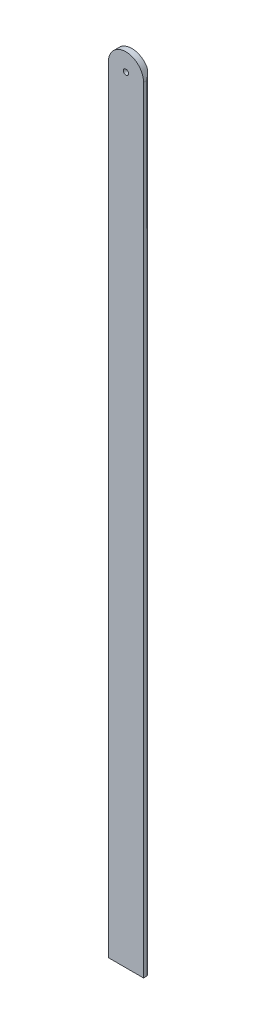
SolidWorks part; units mm, degrees
material "6061 Alloy"
ref_plane "Front Plane" through (0, 0, 0) normal (0, 0, 1) x (1, 0, 0)
ref_plane "Top Plane" through (0, 0, 0) normal (0, 1, 0) x (1, 0, 0)
ref_plane "Right Plane" through (0, 0, 0) normal (1, 0, 0) x (0, 0, -1)
sketch "Sketch2" plane through (0, 0, 0) normal (0, 1, 0) x (1, 0, 0)
  line L0 (0, 0) -> (19.05, 0)
  line L1 (0, 0) -> (0, 19.05)
  line L2 (4.7625, 3.175) -> (17.4625, 3.175)
  line L3 (3.175, 4.7625) -> (3.175, 17.4625)
  line L4 (0, 19.05) -> (1.5875, 19.05)
  line L5 (19.05, 1.5875) -> (19.05, 0)
  line L6 (3.175, 3.175) -> (3.175, 19.05) construction
  line L7 (3.175, 3.175) -> (19.05, 3.175) construction
  arc A0 (3.175, 17.4625) -> (1.5875, 19.05) centre (1.5875, 17.4625) ccw
  arc A1 (3.175, 4.7625) -> (4.7625, 3.175) centre (4.7625, 4.7625) ccw
  arc A2 (17.4625, 3.175) -> (19.05, 1.5875) centre (17.4625, 1.5875) cw
  dimension "D2" = 1.5875
  dimension "D1" = 3.175
extrude "Boss-Extrude1" add sketch "Sketch2" along normal blind 431.8
sketch "Sketch4" plane through (3.175, 0, 0) normal (1, 0, 0) x (0, 0, -1)
  line L0 (19.05, 431.8) -> (19.05, 406.4)
  line L1 (19.05, 431.8) -> (19.05, 0) construction
  line L2 (19.05, 406.4) -> (3.175, 406.4)
  line L3 (3.175, 431.8) -> (3.175, 0) construction
  line L4 (3.175, 406.4) -> (3.175, 431.8)
  line L5 (3.175, 431.8) -> (19.05, 431.8)
extrude "Cut-Extrude1" cut sketch "Sketch4" against normal blind 6.35
sketch "Sketch5" plane through (3.175, 0, 0) normal (-1, 0, 0) x (0, 0, 1)
  line L8 (-4.7625, 406.4) -> (-3.175, 406.4)
  line L9 (-3.175, 406.4) -> (-3.175, 431.8)
  line L10 (-3.175, 431.8) -> (-4.7625, 431.8)
  line L11 (-4.7625, 431.8) -> (-4.7625, 406.4)
  line L12 (-4.7625, 406.4) -> (-3.175, 406.4)
  line L13 (-3.175, 406.4) -> (-3.175, 431.8)
  line L14 (-3.175, 431.8) -> (-4.7625, 431.8)
  line L15 (-4.7625, 431.8) -> (-4.7625, 406.4)
  dimension "D1" = 0
extrude "Cut-Extrude2" cut sketch "Sketch5" against normal blind 6.35
sketch "Sketch6" plane through (3.175, 0, 0) normal (1, 0, 0) x (0, 0, -1)
  line L0 (19.05, 0) -> (3.175, 0) construction
  line L1 (11.1125, 0) -> (11.1125, 15.875) construction
  line L2 (19.05, 406.4) -> (3.175, 406.4) construction
  line L3 (11.1125, 406.4) -> (11.1125, 390.525) construction
  line L4 (11.1125, 15.875) -> (11.1125, 203.2) construction
  line L5 (11.1125, 203.2) -> (11.1125, 390.525) construction
  circle A1 centre (11.1125, 109.5375) radius 1.4224
  circle A2 centre (11.1125, 203.2) radius 1.4224
  circle A3 centre (11.1125, 296.8625) radius 1.4224
  circle A5 centre (11.1125, 11.1125) radius 1.4224
  circle A6 centre (11.1125, 395.2875) radius 1.4224
  point P12 (11.1125, 203.2)
  point P13 (11.1125, 296.8625)
  point P15 (11.1125, 109.5375)
  dimension "D2" = 2.8448
  dimension "D3" = 2.8448
  dimension "D4" = 2.8448
  dimension "D6" = 2.8448
  dimension "D7" = 2.8448
extrude "Cut-Extrude3" cut sketch "Sketch6" against normal blind 5.08
sketch "Sketch7" plane through (0, 431.8, 0) normal (0, 1, 0) x (1, 0, 0)
  line L8 (17.4625, 3.175) -> (0, 3.175)
  line L9 (0, 3.175) -> (0, 0)
  line L10 (0, 0) -> (19.05, 0)
  line L11 (19.05, 0) -> (19.05, 1.5875)
  line L12 (17.4625, 3.175) -> (0, 3.175)
  line L13 (0, 3.175) -> (0, 0)
  line L14 (0, 0) -> (19.05, 0)
  line L15 (19.05, 0) -> (19.05, 1.5875)
  arc A2 (19.05, 1.5875) -> (17.4625, 3.175) centre (17.4625, 1.5875) ccw
  arc A3 (19.05, 1.5875) -> (17.4625, 3.175) centre (17.4625, 1.5875) ccw
  dimension "D1" = 0
extrude "Cut-Extrude4" cut sketch "Sketch7" against normal blind 2.54
sketch "Sketch8" plane through (0, 0, -3.175) normal (0, 0, -1) x (-1, 0, 0)
  line L0 (0, 429.26) -> (0, 419.735) construction
  line L1 (0, 429.26) -> (0, 406.4) construction
  line L2 (0, 419.735) -> (-9.525, 419.735) construction
  circle A0 centre (-9.525, 419.735) radius 1.4224
  dimension "D1" = 2.8448
extrude "Cut-Extrude5" cut sketch "Sketch8" against normal blind 5.08
ref_plane "Plane1" through (0, 0, 2.54) normal (0, 0, 1) x (1, 0, 0)
sketch "Sketch10" plane through (0, 0, -3.175) normal (0, 0, -1) x (-1, 0, 0)
  line L0 (-9.525, 419.735) -> (-19.05, 429.26) construction
  line L6 (0, 419.735) -> (0, 429.26)
  line L7 (0, 429.26) -> (-19.05, 429.26)
  line L8 (-19.05, 419.735) -> (-19.05, 429.26)
  line L10 (0, 429.26) -> (-9.525, 419.735) construction
  arc A2 (0, 419.735) -> (-19.05, 419.735) centre (-9.525, 419.735) ccw
  line M3 (0, 429.26) -> (-17.4625, 429.26)
  line M4 (-17.4625, 429.26) -> (-17.4625, 0)
  line M8 (0, 406.4) -> (0, 429.26)
extrude "Cut-Extrude7" cut sketch "Sketch10" against normal blind 5.08 contours M8 M3 | M4 | M4 region at (2.1276, 427.1324, -3.175) region at (15.5776, 428.0522, -3.175) region at (18.3487, 426.1569, -3.175)
